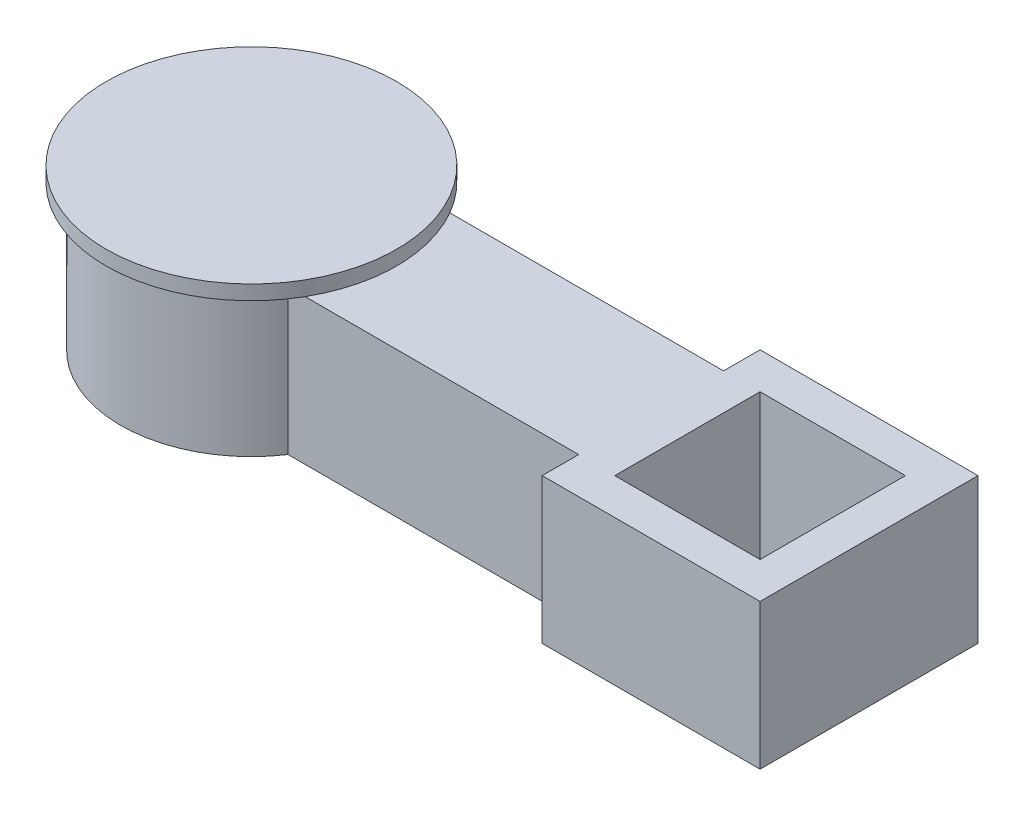
SolidWorks part; units mm, degrees
ref_plane "Front Plane" through (0, 0, 0) normal (0, 0, 1) x (1, 0, 0)
ref_plane "Top Plane" through (0, 0, 0) normal (0, 1, 0) x (1, 0, 0)
ref_plane "Right Plane" through (0, 0, 0) normal (1, 0, 0) x (0, 0, -1)
sketch "Sketch1" plane through (0, 0, 0) normal (0, 1, 0) x (1, 0, 0)
  line L0 (363.1456, 275.7418) -> (363.1456, 275.9924)
  line L1 (363.1456, 175.9924) -> (563.1456, 175.9924)
  line L2 (363.1456, 175.9924) -> (363.1456, 176.2431)
  line L3 (363.1456, 275.9924) -> (563.1456, 275.9924)
  line L4 (563.1456, 175.9924) -> (563.1456, 176.2431)
  line L5 (563.1456, 275.7418) -> (563.1456, 275.9924)
  line L8 (363.1456, 275.9924) -> (563.1456, 275.9924)
  line L9 (363.1456, 275.9924) -> (363.1456, 275.7418)
  line L10 (363.1456, 176.2431) -> (563.1456, 176.2431)
  line L11 (563.1456, 275.9924) -> (563.1456, 176.2431)
  line L12 (563.1456, 301.1178) -> (713.1456, 301.1178)
  line L13 (563.1456, 301.1178) -> (563.1456, 151.1178)
  line L14 (563.1456, 151.1178) -> (713.1456, 151.1178)
  line L15 (713.1456, 301.1178) -> (713.1456, 151.1178)
  arc A0 (363.1456, 275.7418) -> (363.1456, 176.2431) centre (288.1456, 225.9924) ccw
  point P13 (713.1456, 226.1178)
  point P14 (563.1456, 226.1178)
  dimension "D3" = 180
  dimension "D6" = 150
  dimension "D1" = 200
  dimension "D2" = 100
  dimension "D4" = 50
  dimension "D5" = 75
  dimension "D7" = 150
extrude "Boss-Extrude1" add sketch "Sketch1" along normal blind 100 contours L0 A0 L10 L11 L5 L3 | L13 L12 L15 L14 region at (364.9558, 0, -226.0488)
sketch "Sketch5" plane through (0, 100, 0) normal (0, 1, 0) x (1, 0, 0)
  circle A0 centre (288.1456, 225.9924) radius 70
  dimension "D1" = 140
extrude "Cut-Extrude2" cut sketch "Sketch5" against normal blind 100
sketch "Sketch6" plane through (0, 100, 0) normal (0, 1, 0) x (1, 0, 0)
  circle A0 centre (288.1456, 225.9924) radius 100
  dimension "D1" = 200
extrude "Boss-Extrude4" add sketch "Sketch6" along normal blind 10
sketch "Sketch7" plane through (0, 100, 0) normal (0, 1, 0) x (1, 0, 0)
  line L0 (563.1456, 301.1178) -> (713.1456, 301.1178) construction
  line L1 (588.1456, 176.1178) -> (688.1456, 176.1178)
  line L2 (588.1456, 176.1178) -> (588.1456, 276.1178)
  line L3 (588.1456, 276.1178) -> (688.1456, 276.1178)
  line L4 (688.1456, 176.1178) -> (688.1456, 276.1178)
  line L5 (713.1456, 301.1178) -> (713.1456, 151.1178) construction
  point P6 (638.1456, 301.1178)
  point P7 (638.1456, 276.1178)
  point P10 (713.1456, 226.1178)
  point P11 (688.1456, 226.1178)
  dimension "D1" = 100
  dimension "D2" = 100
extrude "Cut-Extrude3" cut sketch "Sketch7" against normal blind 100
